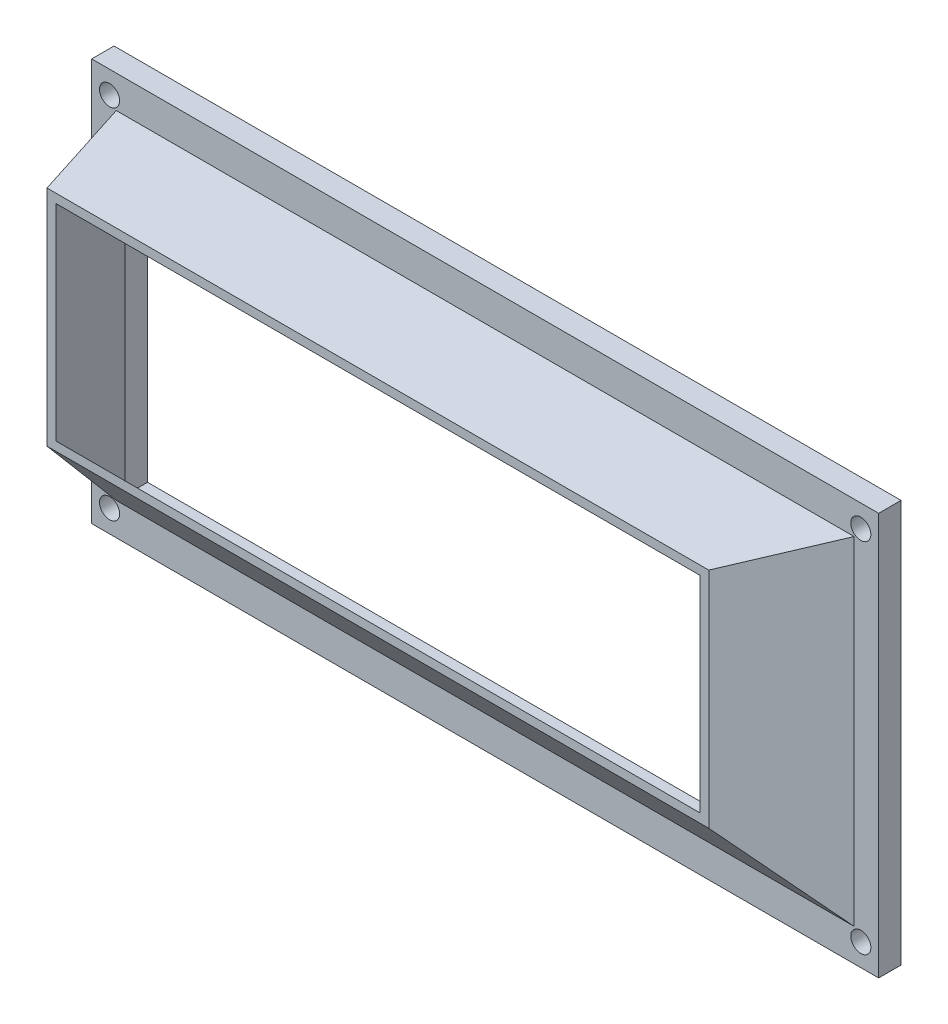
SolidWorks part; units mm, degrees
ref_plane "Front Plane" through (0, 0, 0) normal (0, 0, 1) x (1, 0, 0)
ref_plane "Top Plane" through (0, 0, 0) normal (0, 1, 0) x (1, 0, 0)
ref_plane "Right Plane" through (0, 0, 0) normal (1, 0, 0) x (0, 0, -1)
sketch "Sketch1" plane through (0, 0, 0) normal (0, 0, 1) x (1, 0, 0)
  line L1 (-88, -45) -> (88, -45)
  line L2 (-88, -45) -> (-88, 45)
  line L3 (-88, 45) -> (88, 45)
  line L4 (88, -45) -> (88, 45)
  line L5 (-88, -45) -> (88, 45) construction
  line L6 (-88, 45) -> (88, -45) construction
  line L7 (-80.5, -35.75) -> (80.5, -35.75)
  line L8 (-80.5, -35.75) -> (-80.5, 35.75)
  line L9 (-80.5, 35.75) -> (80.5, 35.75)
  line L10 (80.5, -35.75) -> (80.5, 35.75)
  line L11 (-80.5, -35.75) -> (80.5, 35.75) construction
  line L12 (-80.5, 35.75) -> (80.5, -35.75) construction
  point P0 (0, 0)
  point P6 (0, 0)
  dimension "D1" = 176
  dimension "D2" = 90
  dimension "D3" = 161
  dimension "D4" = 71.5
extrude "Boss-Extrude1" add sketch "Sketch1" along normal blind 5
hole_wizard "M4 Clearance Hole1" positions "Sketch2" profile "Sketch4" hole size "M4" standard "ANSI Metric" end condition through all
sketch "Sketch2" plane through (0, 0, 5) normal (0, 0, 1) x (1, 0, 0)
  line L1 (-84, -40) -> (84, -40)
  line L2 (-84, -40) -> (-84, 40)
  line L3 (-84, 40) -> (84, 40)
  line L4 (84, -40) -> (84, 40)
  line L5 (-84, -40) -> (84, 40) construction
  line L6 (-84, 40) -> (84, -40) construction
  point P2 (84, 40)
  point P157 (-84, -40)
  point P158 (-84, 40)
  point P159 (84, -40)
  dimension "D1" = 168
  dimension "D2" = 80
sketch "Sketch4" plane through (84, 40, 5) normal (1, 0, 0) x (0, -1, 0)
  line L0 (0, 0) -> (0, 5)
  line L1 (0, 5) -> (2.25, 5)
  line L2 (2.25, 5) -> (2.25, 0)
  line L5 (2.25, 0) -> (0, 0)
  line L11 (0, -6.35) -> (0, 107.95) construction
  dimension "Thru Hole Dia." = 4.5
  dimension "Thru Hole Depth" = 5
sketch "Sketch11" plane through (88, 0, 0) normal (1, 0, 0) x (0, 0, -1)
  line L0 (-5, 35.75) -> (-15, 23)
  line L1 (-15, 23) -> (-15, 25)
  line L2 (-15, 25) -> (-5, 37.75)
  line L3 (-5, 35.75) -> (-5, 37.75)
  line L4 (0, -35.75) -> (0, 35.75)
  line L5 (0, 35.75) -> (-5, 35.75)
  line L6 (-5, 35.75) -> (-5, -35.75)
  line L7 (-5, -35.75) -> (0, -35.75)
  line L8 (0, -35.75) -> (0, 35.75)
  line L9 (0, 35.75) -> (-5, 35.75)
  line L10 (-5, 35.75) -> (-5, -35.75)
  line L11 (-5, -35.75) -> (0, -35.75)
  line L12 (0, -45) -> (0, 45)
  line L13 (0, 45) -> (-5, 45)
  line L14 (-5, 45) -> (-5, -45)
  line L15 (-5, -45) -> (0, -45)
  line L16 (0, -45) -> (0, 45)
  line L17 (0, 45) -> (-5, 45)
  line L18 (-5, 45) -> (-5, -45)
  line L19 (-5, -45) -> (0, -45)
  point P6 (0, 0)
  dimension "D3" = 22
  dimension "D4" = 2
  dimension "D5" = 10
  dimension "D1" = 0
  dimension "D2" = 0
extrude "Boss-Extrude7" add sketch "Sketch11" against normal up to vertex (176 mm away) contours L0 L1 L2 L3 up to point (-88, 45, 0)
mirror "Mirror2" about plane through (0, 0, 0) normal (0, 1, 0) of "Boss-Extrude7"
sketch "Sketch12" plane through (0, 45, 0) normal (0, 1, 0) x (1, 0, 0)
  line L0 (-80.5, -5) -> (-86, -15)
  line L1 (-86, -15) -> (-88, -15)
  line L2 (-88, -15) -> (-82.5, -5)
  line L3 (80.5, -5) -> (58, -15)
  line L4 (88, 0) -> (-88, 0)
  line L5 (-88, 0) -> (-88, -5)
  line L6 (-88, -5) -> (88, -5)
  line L7 (88, -5) -> (88, 0)
  line L8 (88, 0) -> (-88, 0)
  line L9 (-88, 0) -> (-88, -5)
  line L10 (-88, -5) -> (88, -5)
  line L11 (88, -5) -> (88, 0)
  line L12 (80.5, 0) -> (-80.5, 0)
  line L13 (-80.5, 0) -> (-80.5, -5)
  line L14 (-80.5, -5) -> (80.5, -5)
  line L15 (80.5, -5) -> (80.5, 0)
  line L16 (80.5, 0) -> (-80.5, 0)
  line L17 (-80.5, 0) -> (-80.5, -5)
  line L18 (-80.5, -5) -> (80.5, -5)
  line L19 (80.5, -5) -> (80.5, 0)
  line L20 (58, -15) -> (60, -15)
  line L21 (60, -15) -> (82.5, -5)
  line L22 (-82.5, -5) -> (-80.5, -5)
  line L23 (80.5, -5) -> (82.5, -5)
  line M16 (-88, -5) -> (88, -5)
  dimension "D3" = 10
  dimension "D4" = 2
  dimension "D5" = 2
  dimension "D6" = 30
  dimension "D7" = 10
  dimension "D1" = 0
  dimension "D2" = 0
extrude "Boss-Extrude8" add sketch "Sketch12" against normal up to vertex (90 mm away) contours L2 L1 L0 M16 | L3 L20 L21 L23 region at (-84.25, 45, 10) up to point (-88, -45, 0)
sketch "Sketch13" plane through (0, 45, 0) normal (0, 1, 0) x (1, 0, 0)
  line L0 (-88, -5) -> (-88, -15)
  line L1 (-88, -5) -> (-82.5, -5)
  line L2 (-88, -15) -> (-88, -5)
  line L3 (60, -15) -> (88, -15)
  line L4 (88, -15) -> (88, -5)
  line L5 (82.5, -5) -> (60, -15)
  line L6 (82.5, -5) -> (88, -5)
  line L7 (88, -5) -> (88, -15)
  line L8 (88, -15) -> (60, -15)
  line L12 (88, 0) -> (-88, 0)
  line L13 (-88, 0) -> (-88, -5)
  line L14 (-88, -5) -> (-82.5, -5)
  line L15 (-82.5, -5) -> (-88, -15)
  line L16 (-88, -15) -> (-86, -15)
  line L17 (-86, -15) -> (-80.5, -5)
  line L18 (-80.5, -5) -> (80.5, -5)
  line L19 (80.5, -5) -> (58, -15)
  line L20 (58, -15) -> (60, -15)
  line L21 (60, -15) -> (82.5, -5)
  line L22 (82.5, -5) -> (88, -5)
  line L23 (88, -5) -> (88, 0)
  line L24 (88, 0) -> (-88, 0)
  line L25 (-88, 0) -> (-88, -5)
  line L26 (-88, -5) -> (-82.5, -5)
  line L27 (-82.5, -5) -> (-88, -15)
  line L28 (-88, -15) -> (-86, -15)
  line L29 (-86, -15) -> (-80.5, -5)
  line L30 (-80.5, -5) -> (80.5, -5)
  line L31 (80.5, -5) -> (58, -15)
  line L32 (58, -15) -> (60, -15)
  line L33 (60, -15) -> (82.5, -5)
  line L34 (82.5, -5) -> (88, -5)
  line L35 (88, -5) -> (88, 0)
  line M15 (-88, -5) -> (-82.5, -5)
  line M16 (-82.5, -5) -> (-88, -15)
  line M22 (60, -15) -> (82.5, -5)
  line M23 (82.5, -5) -> (88, -5)
  dimension "D1" = 0
extrude "Cut-Extrude2" cut sketch "Sketch13" against normal up to vertex (90 mm away) contours L3 L4 M23 M22 | L0 M15 M16 region at (-86.1667, 45, 8.3333) region at (78.3657, 45, 11.1194) up to point (-88, -45, 0)
sketch "Sketch14" plane through (88, 0, 0) normal (1, 0, 0) x (0, 0, -1)
  line L0 (-5, -37.75) -> (-15, -25) construction
  line L1 (-15, -25) -> (-15, -45) construction
  line L2 (-15, -45) -> (-5, -45) construction
  line L3 (-5, -45) -> (-5, -37.75) construction
  line L4 (-15, 45) -> (-15, 25) construction
  line L5 (-15, 25) -> (-5, 37.75) construction
  line L6 (-5, 37.75) -> (-5, 45) construction
  line L7 (-5, 45) -> (-15, 45) construction
  line L8 (-5, -37.75) -> (-15, -25)
  line L9 (-15, -25) -> (-15, -45)
  line L10 (-15, -45) -> (-5, -45)
  line L11 (-5, -45) -> (-5, -37.75)
  line L12 (-15, 45) -> (-15, 25)
  line L13 (-15, 25) -> (-5, 37.75)
  line L14 (-5, 37.75) -> (-5, 45)
  line L15 (-5, 45) -> (-15, 45)
extrude "Cut-Extrude3" cut sketch "Sketch14" against normal up to vertex (176 mm away) up to point (-88, 45, 0)
